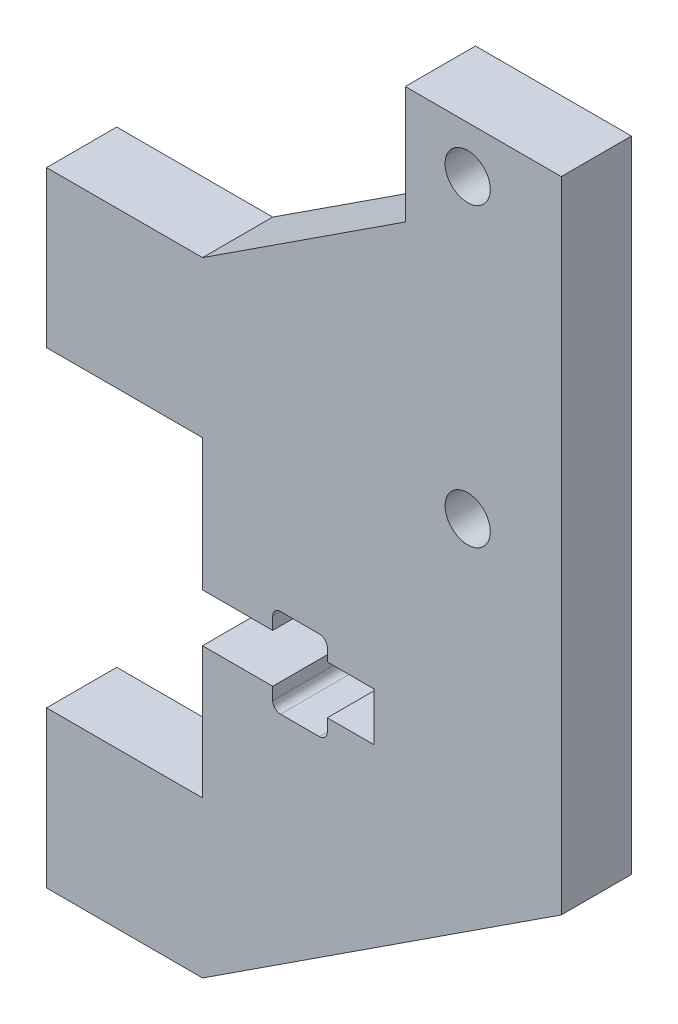
SolidWorks part; units mm, degrees
ref_plane "Front Plane" through (0, 0, 0) normal (0, 0, 1) x (1, 0, 0)
ref_plane "Top Plane" through (0, 0, 0) normal (0, 1, 0) x (1, 0, 0)
ref_plane "Right Plane" through (0, 0, 0) normal (1, 0, 0) x (0, 0, -1)
sketch "Sketch1" plane through (0, 0, 0) normal (0, 0, 1) x (1, 0, 0)
  line L0 (13, 3.4783) -> (0, -5)
  line L1 (0, -5) -> (-10, -5)
  line L2 (-10, -5) -> (-10, -15)
  line L3 (-10, -15) -> (0, -15)
  line L4 (0, -15) -> (0, -35)
  line L5 (0, -35) -> (-10, -35)
  line L6 (-10, -35) -> (-10, -45)
  line L7 (-10, -45) -> (0, -45)
  line L10 (0, -45) -> (23, -30)
  line L11 (23, -30) -> (23, 11)
  line L12 (23, 11) -> (13, 11)
  line L13 (13, 11) -> (13, 3.4783)
  line L15 (0, -5) -> (0, -45) construction
  line L16 (-10, -10) -> (0, -10) construction
  line L17 (-10, -40) -> (0, -40) construction
  line L18 (-10, -15) -> (-10, -35) construction
  line L19 (-10, -25) -> (0, -25) construction
  dimension "D1" = 10
  dimension "D2" = 10
  dimension "D3" = 10
  dimension "D4" = 10
  dimension "D5" = 15
  dimension "D8" = 10
  dimension "D10" = 13
  dimension "D6" = 15
  dimension "D7" = 16
extrude "Boss-Extrude1" add sketch "Sketch1" along normal blind 4.5
sketch "Sketch2" plane through (0, 0, 4.5) normal (0, 0, 1) x (1, 0, 0)
  line L0 (0, -25) -> (23, -25) construction
  line L1 (0, -15) -> (0, -35) construction
  line L3 (11, -26.55) -> (11, -23.45) construction
  line L4 (11, -23.45) -> (0, -23.45) construction
  line L5 (0, -26.55) -> (0, -23.45)
  line L6 (0, -23.45) -> (4.5, -23.45)
  line L7 (4.5, -23.45) -> (4.5, -22.65)
  line L8 (5, -22.15) -> (7.5, -22.15)
  line L9 (8, -22.65) -> (8, -23.45)
  line L10 (8, -23.45) -> (11, -23.45)
  line L11 (11, -23.45) -> (11, -26.55)
  line L12 (11, -26.55) -> (0, -26.55) construction
  line L13 (8, -26.55) -> (11, -26.55)
  line L14 (8, -27.35) -> (8, -26.55)
  line L15 (5, -27.85) -> (7.5, -27.85)
  line L16 (4.5, -26.55) -> (4.5, -27.35)
  line L17 (0, -26.55) -> (4.5, -26.55)
  line L18 (23, -30) -> (23, 11) construction
  arc A0 (7.5, -22.15) -> (8, -22.65) centre (7.5, -22.65) cw
  arc A1 (4.5, -22.65) -> (5, -22.15) centre (5, -22.65) cw
  arc A2 (4.5, -27.35) -> (5, -27.85) centre (5, -27.35) ccw
  arc A3 (7.5, -27.85) -> (8, -27.35) centre (7.5, -27.35) ccw
  point P15 (8, -22.15)
  point P18 (4.5, -22.15)
  point P27 (11, -25)
  point P29 (4.5, -27.85)
  point P30 (8, -27.85)
  dimension "D6" = 0.5
  dimension "D1" = 11
  dimension "D2" = 1.55
  dimension "D3" = 8
  dimension "D4" = 3.5
  dimension "D5" = 2.85
extrude "screw-cutout" cut sketch "Sketch2" against normal through all
sketch "Sketch3" plane through (0, 0, 4.5) normal (0, 0, 1) x (1, 0, 0)
  line L0 (17, 55) -> (17, -45) construction
  line L3 (13, 11) -> (13, 3.4783) construction
  line L5 (-10, -45) -> (0, -45) construction
  line L10 (11, -26.55) -> (11, -23.45) construction
  circle A1 centre (17, 8) radius 1.45
  circle A5 centre (17, -11) radius 1.45
  point P8 (11, -25)
  dimension "D4" = 2.9
  dimension "D11" = 2.9
  dimension "D6" = 4
  dimension "D12" = 19
  dimension "D2" = 14
extrude "Cut-Extrude2" cut sketch "Sketch3" against normal through all
sketch "Sketch4" [suppressed] plane through (0, 0, 4.5) normal (0, 0, 1) x (1, 0, 0)
  line L0 (17, -11) -> (17, 8) construction
  line L1 (17, -1.5) -> (13, -1.5) construction
  line L2 (13, 11) -> (13, 3.4783) construction
  line L4 (15, 2.5) -> (13, 2.5)
  line L5 (15, 2.5) -> (15, -5.5)
  line L6 (15, -5.5) -> (13, -5.5)
  line L7 (13, 2.5) -> (13, -5.5)
  line L8 (15, 2.5) -> (13, -5.5) construction
  line L9 (15, -5.5) -> (13, 2.5) construction
  circle A1 centre (17, 8) radius 1.55 construction
  circle A3 centre (17, -11) radius 1.55 construction
  point P11 (14, -1.5)
  dimension "D1" = 8
  dimension "D2" = 2
  dimension "D3" = 3
equation "\"X-ROD-SPACING\"=45"
equation "\"Y-ROD-SPACING\"=75"
equation "\"Z-ROD-SPACING\"=17.5"
equation "\"Y-BED-OFFSET\"=2"
equation "\"Y-BED-ROD-INSET\"=3.5"
equation "\"T-SLOT-NUT-FILLET-RADIUS\"=0.5"
equation "\"T-SLOT-SCREW-SHAFT-RADIUS\"=1.55"
equation "\"T-SLOT-SCREW-SHAFT-CUTOUT-LENGTH\"=11"
equation "\"T-SLOT-NUT-DEPTH\"=3.5"
equation "\"T-SLOT-NUT-WIDTH\"=2.85"
equation "\"T-SLOT-NUT-END-DISTANCE\"=8"
equation "\"ACRYLIC-THICKNESS\"=10"
equation "\"ACRYLIC-THICKNESS2\"=4.5"
equation "\"ACRYLIC-TAB-CUTOUT-SIZE\"=\"ACRYLIC-THICKNESS\"+\"ACRYLIC-TAB-TOLERANCE\"*2"
equation "\"ACRYLIC-TAB-WIDTH\"=\"ACRYLIC-THICKNESS\""
equation "\"ACRYLIC-M3-HOLE\"=2.9"
equation "\"SMOOTHROD-CAP-SCREW-DISTANCE\"=20"
equation "\"FRAME-WIDTH-INNER\"=370"
equation "\"NEMA17-HOLE-SPACING\"=31"
equation "\"NEMA17-CENTRAL-CUTOUT\"=22.5"
equation "\"Z-BRACKET-REACH\"=57"
equation "\"Z-ROD-INSET\"=13.5"
equation "\"TOP-BRACKET-SPACING\"=40"
equation "\"SMOOTHROD-X-LENGTH\"=350"
equation "\"SMOOTHROD-Y-LENGTH\"=350"
equation "\"SMOOTHROD-Z-LENGTH\"=350"
equation "\"SMOOTHROD-TIGHTENING-HEADROOM\"=.25"
equation "\"LEADSCREW-Z-LENGTH\"=300"
equation "\"SCREW-LENGTH-FRAME\"=\"ACRYLIC-THICKNESS\" + 10"
equation "\"SCREW-HEAD-RADIUS\"=6"
equation "\"PRINTED-X-SMOOTHROD-DIAMETER\"=8.8"
equation "\"PRINTED-X-SMOOTHROD-CUTOUT\"=10"
equation "\"PRINTED-X-BASE-HEIGHT\"=10"
equation "\"PRINTED-LM8UU-CUTOUT-SIZE\"=15.5"
equation "\"PRINTED-LM8UU-CUTOUT-LENGTH\"=24.5"
equation "\"PRINTED-X-IDLER-HEIGHT\"=16"
equation "\"PSU-MOUNTING-WIDTH\"=95"
equation "\"PSU-MOUNTING-HEIGHT\"=177"
equation "\"Y-BELT-TO-ROD-DISTANCE\"=20"
equation "\"SPOOL-HOLDER-ROD-SPACING\"=150"
equation "\"D1@Sketch1\"=\"ACRYLIC-TAB-WIDTH\""
equation "\"D2@Sketch1\"=\"ACRYLIC-TAB-WIDTH\""
equation "\"D3@Sketch1\"=\"ACRYLIC-THICKNESS\""
equation "\"D4@Sketch1\"=\"ACRYLIC-THICKNESS\""
equation "\"D1@Boss-Extrude1\"=\"ACRYLIC-THICKNESS2\""
equation "\"D1@Sketch2\"=\"T-SLOT-SCREW-SHAFT-CUTOUT-LENGTH\""
equation "\"D2@Sketch2\"=\"T-SLOT-SCREW-SHAFT-RADIUS\""
equation "\"D3@Sketch2\"=\"T-SLOT-NUT-END-DISTANCE\""
equation "\"D4@Sketch2\"=\"T-SLOT-NUT-DEPTH\""
equation "\"D5@Sketch2\"=\"T-SLOT-NUT-WIDTH\""
equation "\"D6@Sketch2\"=\"T-SLOT-NUT-FILLET-RADIUS\""
equation "\"D4@Sketch3\"=\"ACRYLIC-M3-HOLE\""
equation "\"D11@Sketch3\"=\"ACRYLIC-M3-HOLE\""
equation "\"Y-BED-SCREW-SPACING\"=209"
equation "\"Y-BED-SCREW-CUTOUT-SLOT-HEIGHT\"=2.5"
equation "\"ACRYLIC-TAB-TOLERANCE\"=-.05"
equation "\"SCREW-LENGTH-MOTOR\"=\"ACRYLIC-THICKNESS\" + 5"
equation "\"SCREW-LENGTH-EXTRUDER\"=28"
equation "\"PRINTED-M3-HOLE\"=3.5"
equation "\"ACRYLIC-X-CARRIAGE-WIDTH\"=55"
equation "\"ACRYLIC-X-CARRIAGE-HEIGHT\"=75"
equation "\"ACRYLIC-X-CARRIAGE-LM8UU-CUTOUT-WIDTH\"=24.25"
equation "\"ACRYLIC-X-CARRIAGE-LM8UU-CUTOUT-HEIGHT\"=11.0"
equation "\"ACRYLIC-X-CARRIAGE-SCREW-SPACING-X\"=15"
equation "\"ACRYLIC-X-CARRIAGE-SCREW-SPACING-Y\"=33"
equation "\"ACRYLIC-X-CARRIAGE-CENTER-TAB-SPACING\"=14"
equation "\"ACRYLIC-X-CARRIAGE-EXTRUDER-OFFSET\"=26"
equation "\"ACRYLIC-X-CARRIAGE-EXTRUDER-ANGLE\"=90"
equation "\"ACRYLIC-X-CARRIAGE-EXTRUDER-SHELF-DEPTH\"=\"ACRYLIC-X-CARRIAGE-EXTRUDER-OFFSET\" + 28"
equation "\"ACRYLIC-X-CARRIAGE-EXTRUDER-BRACE-SPACING\"=23"
equation "\"ACRYLIC-X-CARRIAGE-EXTRUDER-BRACE-TAB-OFFSET\"=20"
equation "\"ACRYLIC-X-CARRIAGE-EXTRUDER-BRACE-HEIGHT\"=35"
equation "\"ACRYLIC-X-CARRIAGE-EXTRUDER-BRACE-SCREW-SPACING\"=22"
equation "\"ACRYLIC-X-CARRIAGE-DUAL-WIDTH-MULTIPLIER\"=1.65"
equation "\"ACRYLIC-X-CARRIAGE-DUAL-HOTEND-SPACING\"=42"
equation "\"ACRYLIC-X-CARRIAGE-DUAL-WIDTH\"=75"
equation "\"ACRYLIC-X-CARRIAGE-DUAL-HOTEND-SEPARATION\"=36"
equation "\"ACRYLIC-X-CARRIAGE-DUAL-MOUNT-PLATE-DEPTH\"=75"
equation "\"ACRYLIC-X-CARRIAGE-DUAL-MOUNT-BRACE-WIDTH\"=33"
equation "\"ACRYLIC-X-CARRIAGE-DUAL-MOUNT-SCREW-WIDTH\"=40"
equation "\"BLOWER-FAN-WIDTH\"=15"
